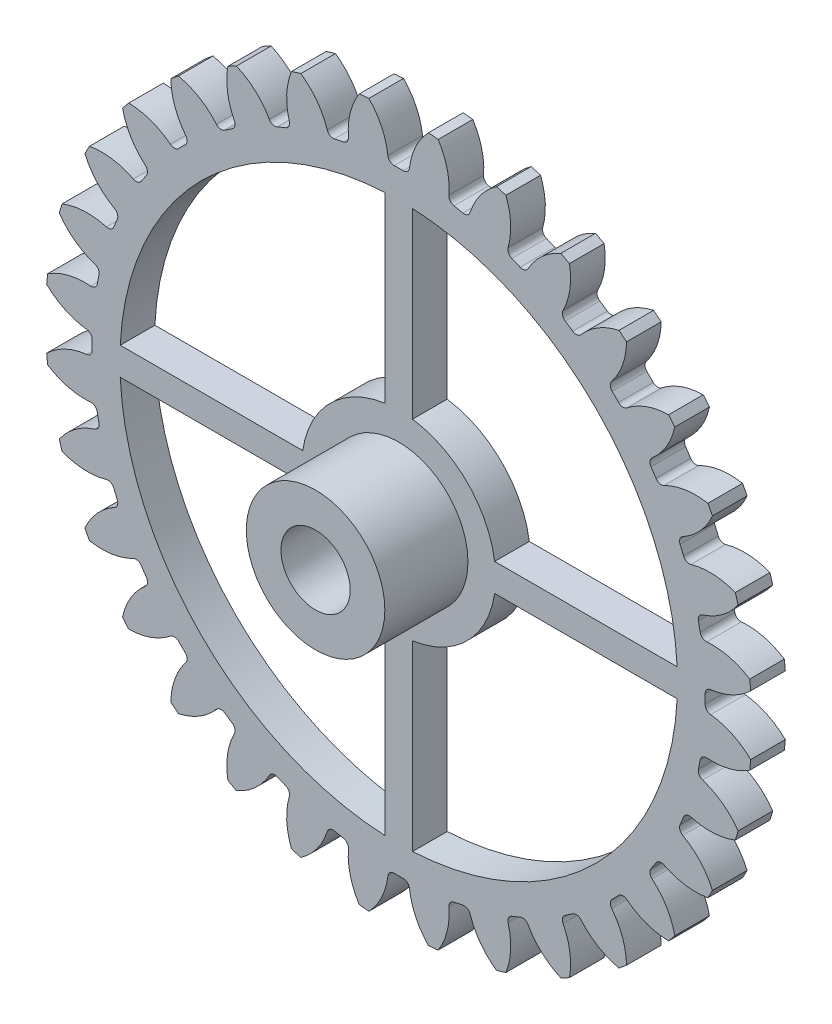
SolidWorks part; units mm, degrees
material "6061-T6 (SS)"
ref_plane "Front Plane" through (0, 0, 0) normal (0, 0, 1) x (1, 0, 0)
ref_plane "Top Plane" through (0, 0, 0) normal (0, 1, 0) x (1, 0, 0)
ref_plane "Right Plane" through (0, 0, 0) normal (1, 0, 0) x (0, 0, -1)
sketch "Sketch1" plane through (0, 0, 0) normal (0, 0, 1) x (1, 0, 0)
  circle A0 centre (0, 0) radius 48
  circle A1 centre (0, 0) radius 51
  circle A2 centre (0, 0) radius 44.25
  dimension "D1" = 96
  dimension "D2" = 102
  dimension "D3" = 6.75
extrude "Boss-Extrude1" add sketch "Sketch1" along normal mid plane 5 contours A1
sketch "Sketch2" plane through (0, 0, 0) normal (0, 0, 1) x (1, 0, 0)
  line L0 (0, 0) -> (0, 51) construction
  line L1 (-2.3552, 47.9422) -> (2.3552, 47.9422) construction
  line L2 (-1.499, 44.2246) -> (0, 0) construction
  line L3 (0, 42.6522) -> (-4.0902, 51.8389) construction
  line L4 (0, 0) -> (4.9989, 50.7544) construction
  line L5 (2.3552, 47.9422) -> (7.0431, 47.4805) construction
  circle A0 centre (0, 0) radius 51 construction
  arc A1 (-5.306, 51.7286) -> (-1.499, 44.2246) centre (-11.4637, 43.8869) cw
  arc A2 (5.306, 51.7286) -> (1.499, 44.2246) centre (11.4637, 43.8869) ccw
  circle A3 centre (0, 0) radius 44.25 construction
  arc A4 (1.499, 44.2246) -> (-1.499, 44.2246) centre (0, 0) ccw
  circle A6 centre (0, 0) radius 48 construction
  circle A7 centre (0, 0) radius 52
  arc A8 (5.306, 51.7286) -> (-5.306, 51.7286) centre (0, 0) ccw
  circle A9 centre (0, 0) radius 51 construction
  dimension "D2" = 24
  dimension "D3" = 5.625
extrude "Cut-Extrude1" cut sketch "Sketch2" against normal through all both and the other way through all
fillet "Fillet1" radius 0.9 2 edges at (1.499, 44.2246, 0) (-1.499, 44.2246, 0)
pattern_circular "CirPattern1" count 32 over 360 about axis through (0, 0, 2.5) along (0, 0, 1) of "Cut-Extrude1", "Fillet1"
sketch "Sketch3" plane through (0, 0, 2.5) normal (0, 0, 1) x (1, 0, 0)
  circle A0 centre (0, 0) radius 10
  dimension "D1" = 20
extrude "Boss-Extrude2" add sketch "Sketch3" along normal blind 12
sketch "Sketch4" plane through (0, 0, 2.5) normal (0, 0, 1) x (1, 0, 0)
  line L0 (0, 0) -> (0, 44.25) construction
  line L1 (-2, 13.8564) -> (-2, 40.2003)
  line L2 (2, 13.8564) -> (2, 40.2003)
  line L3 (13.8564, 2) -> (40.2003, 2)
  line L4 (13.8564, -2) -> (40.2003, -2)
  line L5 (2, -13.8564) -> (2, -40.2003)
  line L6 (-2, -13.8564) -> (-2, -40.2003)
  line L7 (-13.8564, -2) -> (-40.2003, -2)
  line L8 (-13.8564, 2) -> (-40.2003, 2)
  circle A0 centre (0, 0) radius 44.25 construction
  circle A3 centre (0, 0) radius 40.25
  arc A4 (-2, 40.2003) -> (-40.2003, 2) centre (0, 0) ccw
  arc A5 (-13.8564, -2) -> (-2, -13.8564) centre (0, 0) ccw
  circle A6 centre (0, 0) radius 14
  arc A7 (-2, 13.8564) -> (-13.8564, 2) centre (0, 0) ccw
  arc A8 (-40.2003, -2) -> (-2, -40.2003) centre (0, 0) ccw
  arc A9 (13.8564, 2) -> (2, 13.8564) centre (0, 0) ccw
  arc A10 (40.2003, 2) -> (2, 40.2003) centre (0, 0) ccw
  arc A11 (2, -13.8564) -> (13.8564, -2) centre (0, 0) ccw
  arc A12 (2, -40.2003) -> (40.2003, -2) centre (0, 0) ccw
  circle A13 centre (0, 0) radius 5
  point P15 (2, 27.0283)
  point P31 (0, 0)
  dimension "D5" = 10
  dimension "D3" = 4
  dimension "D1" = 4
  dimension "D2" = 4
  dimension "D4" = 4
extrude "Cut-Extrude2" cut sketch "Sketch4" against normal through all both and the other way through all contours A13 | L2 A10 L3 A9 | L4 A12 L5 A11 | L7 A8 L6 A5 | A4 L8 A7 L1
equation "\"Module\"= 3mm"
equation "\"Number of Teeth\"= 32"
equation "\"D1@Sketch1\"=\"Module\" * \"Number of Teeth\""
equation "\"D2@Sketch1\"=(\"Number of Teeth\" + 2) * \"Module\""
equation "\"D3@Sketch1\"=\"Module\" * if( \"Module\"=>1.25,2.25,2.4)"
equation "\"Pressure Angle\"= 24deg"
equation "\"D2@Sketch2\"=\"Pressure Angle\""
equation "\"D3@Sketch2\"=180 / \"Number of Teeth\""
equation "\"D1@Fillet1\"=0.3 * \"Module\""
equation "\"D1@CirPattern1\"=\"Number of Teeth\""
